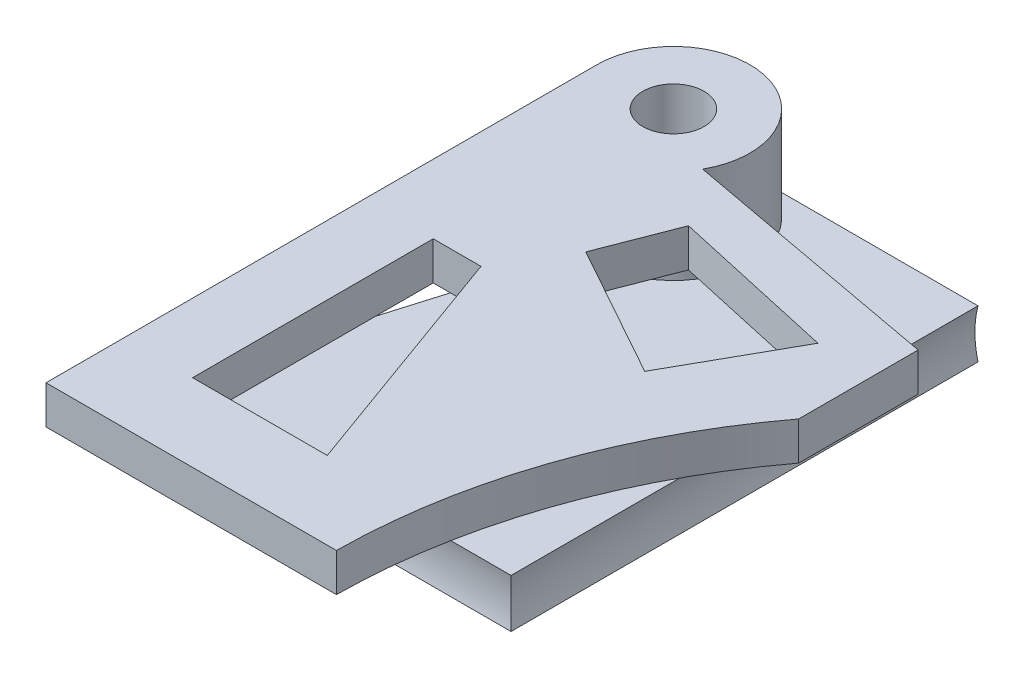
SolidWorks part; units mm, degrees
note: The reader was unsure of these and kept them because the rebuilt part matched: shared geometry of "Sketch1<3>".
ref_plane "Front Plane" through (0, 0, 0) normal (0, 0, 1) x (1, 0, 0)
ref_plane "Top Plane" through (0, 0, 0) normal (0, 1, 0) x (1, 0, 0)
ref_plane "Right Plane" through (0, 0, 0) normal (1, 0, 0) x (0, 0, -1)
sketch "Sketch1" plane through (0, 0, 0) normal (0, 1, 0) x (1, 0, 0)
  line L6 (30.8201, 40.3482) -> (30.8201, -20.6518)
  line L8 (30.8201, -20.6518) -> (-13.4276, -20.6518)
  line L9 (42.9102, -20.6518) -> (-457.0898, -20.6518) construction
  line L10 (-13.4276, -20.6518) -> (-1.1714, 20.6186)
  line L13 (30.8201, 40.3482) -> (1.7979, 40.3482)
  circle A0 centre (1, 30.38) radius 4
  circle A1 centre (1, 30.38) radius 10
  dimension "D2" = 20
  dimension "D3" = 8
  dimension "D1" = 61
extrude "Boss-Extrude1" add sketch "Sketch1" along normal blind 6.35
extrude "Boss-Extrude2" add sketch "Sketch1<3>" along normal blind 18.7
sketch "Sketch1<3>" plane through (0, 0, 0) normal (0, 1, 0) x (1, 0, 0) same geometry as "Sketch1"
ref_plane "Plane1" through (0, 9.35, 0) normal (0, 1, 0) x (1, 0, 0)
sketch "Sketch3" plane through (0, 0, 0) normal (0, 0, 1) x (1, 0, 0)
  line L0 (30.8201, 3.175) -> (121.9702, 3.175) construction
  line L1 (30.8201, 6.35) -> (30.8201, 0) construction
  circle A0 centre (42.9102, 3.175) radius 12.5
  dimension "D1" = 25
extrude "Cut-Extrude1" cut sketch "Sketch3" against normal through all both and the other way through all
sketch "Sketch4" plane through (0, 0, 0) normal (1, 0, 0) x (0, 0, -1)
  line L0 (-35.1146, 3.175) -> (-60.5591, 3.175) construction
  circle A0 centre (-32.7419, 3.175) radius 12.5
  dimension "D1" = 25
extrude "Cut-Extrude3" cut sketch "Sketch4" along normal through all both and the other way through all
sketch "Sketch5" plane through (0, 18.7, 0) normal (0, 1, 0) x (1, 0, 0)
  line L0 (-9, 30.38) -> (-9, -41.5829)
  line L5 (0, -31.4363) -> (0, 0)
  line L6 (9.7166, 25.479) -> (57.0112, 16.7371)
  line L7 (-9, -41.5829) -> (28.9389, -41.5829)
  line L8 (44.2561, 19.0948) -> (44.2561, 3.4948)
  line L9 (0, 0) -> (6.2423, 0)
  line L12 (17.595, -31.4363) -> (0, -31.4363)
  line L13 (11.4551, 8.4817) -> (15.2018, 18.1471)
  line L14 (15.2018, 18.1471) -> (36.949, 13.3144)
  line L15 (36.949, 13.3144) -> (28.816, -1.1837)
  line L16 (28.816, -1.1837) -> (11.4551, 8.4817)
  line L17 (6.2423, 0) -> (17.595, -31.4363)
  circle A0 centre (1, 30.38) radius 10 construction
  circle A1 centre (1, 30.38) radius 4
  circle A2 centre (1, 30.38) radius 10
  arc A4 (57.0112, 16.7371) -> (28.9389, -41.5829) centre (105.0586, -42.3067) ccw
extrude "Boss-Extrude3" add sketch "Sketch5" against normal blind 5
